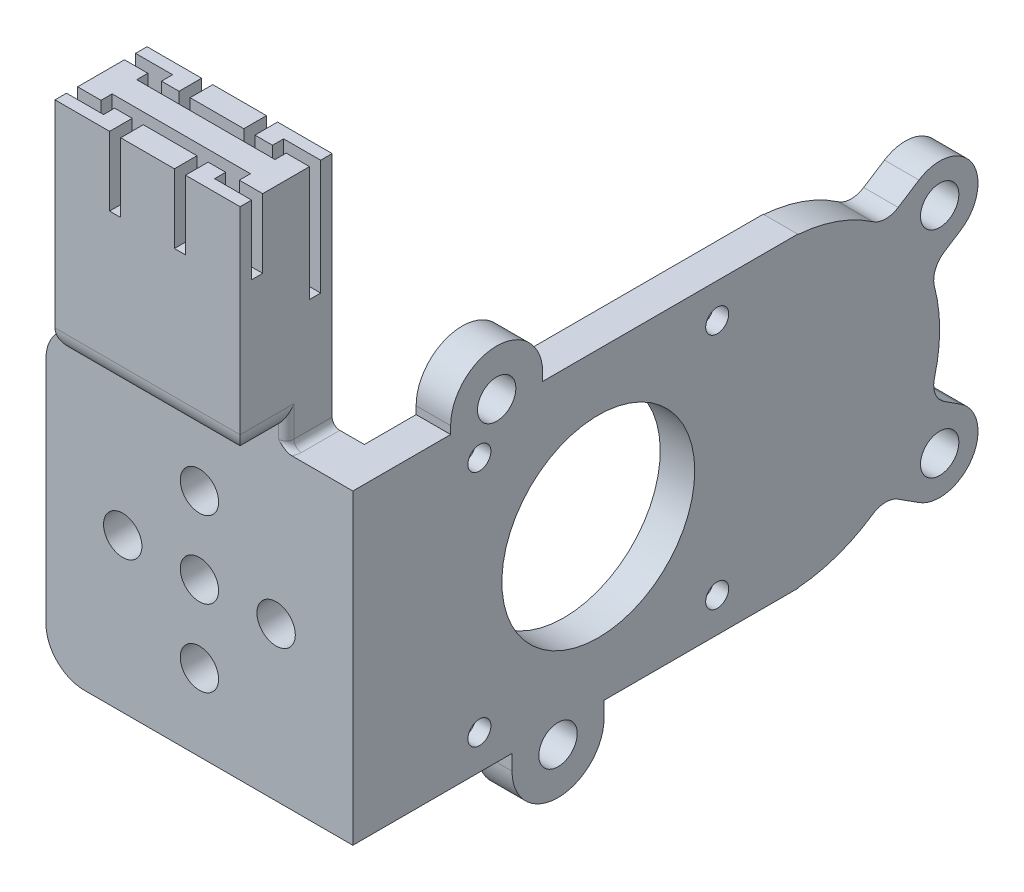
SolidWorks part; units mm, degrees
ref_plane "Front Plane" through (0, 0, 0) normal (0, 0, 1) x (1, 0, 0)
ref_plane "Top Plane" through (0, 0, 0) normal (0, 1, 0) x (1, 0, 0)
ref_plane "Right Plane" through (0, 0, 0) normal (1, 0, 0) x (0, 0, -1)
sketch "Sketch2" plane through (0, 0, 0) normal (0, 0, 1) x (1, 0, 0)
  line L0 (0, 10) -> (0, -10) construction
  line L5 (-20, 20) -> (20, 20)
  line L6 (-20, 20) -> (-20, -20)
  line L7 (-20, -20) -> (20, -20)
  line L8 (20, 20) -> (20, -20)
  line L9 (-10, 0) -> (10, 0) construction
  circle A0 centre (0, 0) radius 2.5
  circle A1 centre (0, 10) radius 2.5
  circle A2 centre (0, -10) radius 2.5
  circle A3 centre (-10, 0) radius 2.5
  circle A4 centre (10, 0) radius 2.5
  point P15 (0, 0)
  point P17 (0, 20)
  point P19 (0, 0)
  point P21 (-20, 0)
  dimension "D3" = 5
  dimension "D1" = 20
  dimension "D2" = 20
  dimension "D4" = 40
  dimension "D5" = 40
extrude "Boss-Extrude1" add sketch "Sketch2" against normal blind 6
sketch "Sketch3" plane through (0, 0, -6) normal (0, 0, -1) x (-1, 0, 0)
  line L0 (20, -20) -> (-20, -20) construction
  line L1 (-20, 20) -> (-15.5, 20)
  line L2 (-20, 20) -> (-20, -20)
  line L3 (-20, -20) -> (-15.5, -20)
  line L4 (-15.5, 20) -> (-15.5, -20)
  dimension "D1" = 4.5
extrude "Boss-Extrude2" add sketch "Sketch3" along normal blind 52
sketch "Sketch4" plane through (15.5, 0, 0) normal (-1, 0, 0) x (0, 0, 1)
  line L0 (-6, 0) -> (-58, 0) construction
  line L1 (-6, 20) -> (-6, -20) construction
  line L2 (-58, -20) -> (-58, 20) construction
  circle A0 centre (-32, 0) radius 12.5732
  circle A1 centre (-16.5, 15.5) radius 1.5
  circle A2 centre (-16.5, -15.5) radius 1.5
  circle A3 centre (-47.5, -15.5) radius 1.5
  circle A4 centre (-47.5, 15.5) radius 1.5
  point P19 (-32, 0)
  dimension "D3" = 3
  dimension "D1" = 15.5
  dimension "D4" = 15.5
  dimension "D2" = 4
extrude "Cut-Extrude1" cut sketch "Sketch4" against normal up to next
sketch "Sketch5" plane through (0, 0, -6) normal (0, 0, -1) x (-1, 0, 0)
  circle A0 centre (0, 10) radius 4.5
  circle A1 centre (0, 0) radius 4.5
  circle A2 centre (10, 0) radius 4.5
  circle A3 centre (0, -10) radius 4.5
  circle A4 centre (-10, 0) radius 4.5
  dimension "D1" = 9
extrude "Cut-Extrude2" cut sketch "Sketch5" against normal blind 1.5
sketch "Sketch6" plane through (15.5, 0, 0) normal (-1, 0, 0) x (0, 0, 1)
  circle A0 centre (-16.5, 15.5) radius 3
  circle A1 centre (-47.5, 15.5) radius 3
  circle A2 centre (-47.5, -15.5) radius 3
  circle A3 centre (-16.5, -15.5) radius 3
  dimension "D1" = 6
extrude "Cut-Extrude3" cut sketch "Sketch6" against normal blind 2.5
fillet "Fillet1" radius 5 2 edges at (-20, -20, -3) (-20, 20, -3)
sketch "Sketch7" plane through (0, 20, 0) normal (0, 1, 0) x (1, 0, 0)
  line L0 (11.3015, -6) -> (-12.8253, -6)
  line L5 (-12.8253, -6) -> (-12.8253, -4.5)
  line L16 (6.4761, 3.0522) -> (-7.9999, 3.0522)
  line L22 (15.5, 6) -> (-15, 6) construction
  line L23 (6.4761, -4.5) -> (6.4761, -3.0522)
  line L26 (11.3015, 6) -> (11.3015, 4.5)
  line L27 (-12.8253, 3.0522) -> (-12.8253, -3.0522)
  line L28 (11.3015, 3.0522) -> (11.3015, -3.0522)
  line L29 (-7.9999, 4.5) -> (-12.8253, 4.5)
  line L30 (-9.7777, 3.0522) -> (-12.8253, 3.0522)
  line L31 (-7.9999, 4.5) -> (-7.9999, 3.0522)
  line L32 (-9.7777, 3.0522) -> (-9.7777, 1.6022)
  line L33 (8.2539, 1.6022) -> (-9.7777, 1.6022)
  line L34 (8.2539, 3.0522) -> (8.2539, 1.6022)
  line L35 (11.3015, 3.0522) -> (8.2539, 3.0522)
  line L36 (11.3015, 4.5) -> (6.4761, 4.5)
  line L37 (6.4761, 4.5) -> (6.4761, 3.0522)
  line L38 (-12.8253, 6) -> (-12.8253, 4.5)
  line L40 (11.3015, 6) -> (-12.8253, 6)
  line L41 (11.3015, -4.5) -> (6.4761, -4.5)
  line L42 (11.3015, -3.0522) -> (8.2539, -3.0522)
  line L43 (8.2539, -3.0522) -> (8.2539, -1.6022)
  line L44 (8.2539, -1.6022) -> (-9.7777, -1.6022)
  line L45 (-9.7777, -3.0522) -> (-9.7777, -1.6022)
  line L46 (-7.9999, -4.5) -> (-7.9999, -3.0522)
  line L47 (-9.7777, -3.0522) -> (-12.8253, -3.0522)
  line L48 (-7.9999, -4.5) -> (-12.8253, -4.5)
  line L49 (11.3015, -6) -> (11.3015, -4.5)
  line L52 (6.4761, -3.0522) -> (-7.9999, -3.0522)
extrude "Boss-Extrude3" add sketch "Sketch7" along normal blind 15 from offset 15.748 separate body
sketch "Sketch18" plane through (0, 35.748, 0) normal (0, -1, 0) x (1, 0, 0)
  line L1 (-12.8253, 6) -> (11.3015, 6)
  line L2 (-12.8253, 6) -> (-12.8253, -6)
  line L3 (-12.8253, -6) -> (11.3015, -6)
  line L4 (11.3015, 6) -> (11.3015, -6)
extrude "Boss-Extrude12" add sketch "Sketch18" along normal up to surface (15.748 mm away) up to face at (6.8333, 20, -21.3333)
sketch "Sketch9" plane through (15.5, 0, 0) normal (-1, 0, 0) x (0, 0, 1)
  line L0 (-32.75, -22) -> (-32.75, -18.4344)
  line L3 (-32.75, -18.4344) -> (-20.75, -18.4344)
  line L5 (-20.75, -18.4344) -> (-20.75, -22)
  line L6 (-24.75, 21) -> (-24.75, 17.6037)
  line L9 (-24.75, 17.6037) -> (-12.75, 17.6037)
  line L11 (-12.75, 17.6037) -> (-12.75, 21)
  circle A0 centre (-18.75, 21) radius 2.5
  arc A1 (-12.75, 21) -> (-24.75, 21) centre (-18.75, 21) ccw
  circle A2 centre (-26.75, -22) radius 2.5
  arc A3 (-32.75, -22) -> (-20.75, -22) centre (-26.75, -22) ccw
  arc A4 (-12.9, 22.3333) -> (-24.6, 22.3333) centre (-18.75, 21) ccw construction
  arc A5 (-32.7128, -22.6667) -> (-20.7872, -22.6667) centre (-26.75, -22) ccw construction
sketch "Sketch11" plane through (15.5, 0, 0) normal (-1, 0, 0) x (0, 0, 1)
  line L0 (-56.5, 20) -> (-56.5, -20)
  line L1 (-73.7993, 18.2079) -> (-69.332, 15.3408)
  line L2 (-79.2007, 9.7921) -> (-75.1596, 7.1985)
  line L3 (-79.2007, -9.7921) -> (-75.1596, -7.1985)
  line L4 (-73.7993, -18.2079) -> (-69.332, -15.3408)
  line L6 (-58, 20) -> (-24.75, 20) construction
  line L7 (-58, -20) -> (-32.75, -20) construction
  arc A0 (-56.5, 20) -> (-56.5, -20) centre (-56.5, 0) ccw
  arc A1 (-75.8257, 5.1494) -> (-75.8257, -5.1494) centre (-56.5, 0) ccw construction
  circle A2 centre (-76.5, 14) radius 2.5
  arc A3 (-73.7993, 18.2079) -> (-79.2007, 9.7921) centre (-76.5, 14) ccw
  circle A4 centre (-76.5, -14) radius 2.5
  arc A5 (-79.2007, -9.7921) -> (-73.7993, -18.2079) centre (-76.5, -14) ccw
  line M15 (-58, 20) -> (-58, -20)
extrude "Boss-Extrude6" add sketch "Sketch11" against normal up to surface (4.5 mm away) contours A0 M15 | L1 A3 L2 A0 A2 | L3 A5 L4 A0 A4 region at (15.5, 0, -65.8044) region at (15.5, 11.7389, -72.9014) region at (15.5, -16.6317, -71.6572) up to face at (20, 15.5, -49)
fillet "Fillet2" radius 3 4 edges at (17.75, -15.3408, -69.332) (17.75, 15.3408, -69.332) (17.75, -7.1985, -75.1596) (17.75, 7.1985, -75.1596)
sketch "Sketch15" plane through (15.5, 0, 0) normal (-1, 0, 0) x (0, 0, 1)
  circle A0 centre (-16.5, 15.5) radius 3
  arc A1 (-18.6388, 17.6037) -> (-14.3612, 17.6037) centre (-16.5, 15.5) ccw construction
extrude "Boss-Extrude13" add sketch "Sketch9" against normal up to surface (4.5 mm away) up to face at (20, 15.5, -49)
sketch "Sketch19" plane through (15.5, 0, 0) normal (-1, 0, 0) x (0, 0, 1)
  circle A0 centre (-18.75, 21) radius 2.5
  circle A1 centre (-26.75, -22) radius 2.5
  arc A2 (-16.4587, 20) -> (-21.0413, 20) centre (-18.75, 21) ccw construction
  arc A3 (-28.25, -20) -> (-25.25, -20) centre (-26.75, -22) ccw construction
extrude "Cut-Extrude7" cut sketch "Sketch19" against normal up to surface (4.5 mm away) up to face at (20, -0.0769, -50.4635)
extrude "Cut-Extrude8" cut sketch "Sketch15" against normal up to surface (2.5 mm away) up to face at (18, 15.0519, -16.5)
sketch "Sketch21" plane through (0, 0, 6) normal (0, 0, 1) x (1, 0, 0)
  line L0 (11.3015, 20) -> (11.3015, 50.748) construction
  line L1 (-12.8253, 20) -> (11.3015, 20)
  line L2 (-12.8253, 20) -> (-12.8253, 22)
  line L3 (-12.8253, 22) -> (11.3015, 22)
  line L4 (11.3015, 20) -> (11.3015, 22)
  dimension "D1" = 2
extrude "Cut-Extrude9" cut sketch "Sketch21" against normal blind 6
sketch "Sketch22" plane through (0, 0, 6) normal (0, 0, 1) x (1, 0, 0)
  line L0 (-12.8253, 50.748) -> (11.3015, 50.748) construction
  line L1 (-5.7119, 50.748) -> (-4.2619, 50.748)
  line L2 (-5.7119, 50.748) -> (-5.7119, 35.748)
  line L3 (-5.7119, 35.748) -> (-4.2619, 35.748)
  line L4 (-4.2619, 50.748) -> (-4.2619, 35.748)
  line L5 (8.2539, 35.748) -> (11.3015, 35.748) construction
  line L6 (2.7381, 50.748) -> (4.1881, 50.748)
  line L7 (2.7381, 50.748) -> (2.7381, 35.748)
  line L8 (2.7381, 35.748) -> (4.1881, 35.748)
  line L9 (4.1881, 50.748) -> (4.1881, 35.748)
  line L10 (-0.7619, 50.748) -> (-0.7619, 27.0452) construction
  dimension "D1" = 1.45
  dimension "D2" = 1.45
  dimension "D3" = 7
  dimension "D4" = 3.5
extrude "Cut-Extrude10" cut sketch "Sketch22" against normal blind 3
ref_plane "Plane2" through (0, 0, 0) normal (0, 0, 1) x (1, 0, 0)
mirror "Mirror6" about plane through (0, 0, 0) normal (0, 0, 1) of "Cut-Extrude10"
sketch "Sketch23" plane through (0, 35.748, 0) normal (0, 1, 0) x (1, 0, 0)
  line L0 (11.3015, 0) -> (11.3015, -6) construction
  line L1 (11.3015, -1.6022) -> (-12.8253, -1.6022)
  line L2 (11.3015, -1.6022) -> (11.3015, -6)
  line L3 (11.3015, -6) -> (-12.8253, -6)
  line L4 (-12.8253, -1.6022) -> (-12.8253, -6)
  line L5 (-5.7119, -6) -> (-4.2619, -6) construction
  line L6 (-12.8253, 0) -> (-12.8253, -6) construction
  line L7 (-9.7777, -1.6022) -> (8.2539, -1.6022) construction
extrude "Boss-Extrude14" add sketch "Sketch23" along normal blind 6
fillet "Fillet4" radius 3 3 edges at (11.3015, 22, 3) (-12.8253, 22, 3) (-0.7619, 22, 6)
fillet "Fillet5" radius 1 2 edges at (-12.8253, 22.5, 0) (11.3015, 22.5, 0)
fillet "Fillet6" radius 1 4 edges at (-12.5324, 20, -0.2929) (11.0086, 20, -0.2929) (-12.8253, 20, -3.5) (11.3015, 20, -3.5)
